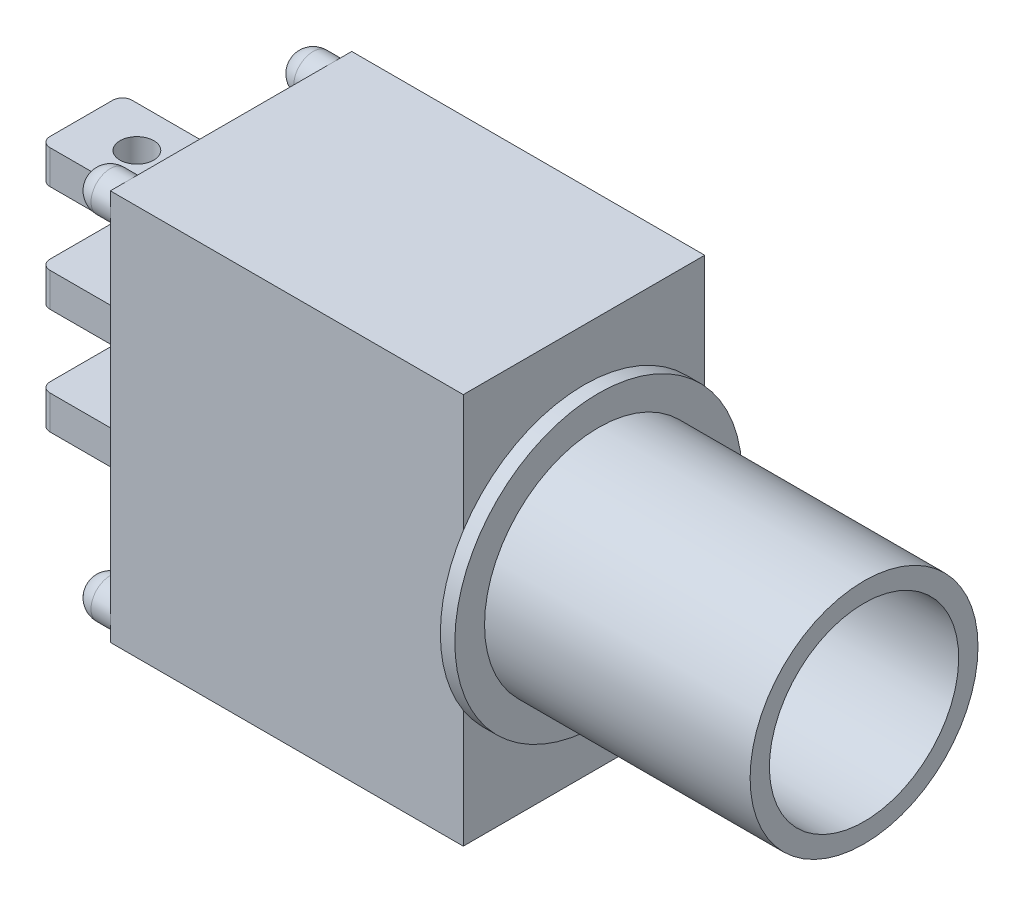
SolidWorks part; units mm, degrees
ref_plane "Front Plane" through (0, 0, 0) normal (0, 0, 1) x (1, 0, 0)
ref_plane "Top Plane" through (0, 0, 0) normal (0, 1, 0) x (1, 0, 0)
ref_plane "Right Plane" through (0, 0, 0) normal (1, 0, 0) x (0, 0, -1)
sketch "Sketch1" plane through (0, 0, 0) normal (0, 0, 1) x (1, 0, 0)
  line L1 (-3.655, 4.05) -> (3.655, 4.05)
  line L2 (-3.655, 4.05) -> (-3.655, -4.05)
  line L3 (-3.655, -4.05) -> (3.655, -4.05)
  line L4 (3.655, 4.05) -> (3.655, -4.05)
  line L5 (-3.655, 4.05) -> (3.655, -4.05) construction
  line L6 (-3.655, -4.05) -> (3.655, 4.05) construction
  point P0 (0, 0)
  dimension "D1" = 7.31
  dimension "D2" = 8.1
extrude "Boss-Extrude1" add sketch "Sketch1" along normal blind 2.5 and the other way blind 2.5
sketch "Sketch2" plane through (-3.655, 0, 0) normal (-1, 0, 0) x (0, 0, 1)
  line L0 (-2.5, 4.05) -> (2.5, 4.05) construction
  line L1 (2.5, 4.05) -> (2.5, -4.05) construction
  line L2 (0, 4.05) -> (0, -4.05) construction
  line L3 (-2.5, -4.05) -> (2.5, -4.05) construction
  line L4 (-2.5, 0) -> (2.5, 0) construction
  line L5 (-2.5, 4.05) -> (-2.5, -4.05) construction
  circle A0 centre (2.1, 3.65) radius 0.4
  circle A1 centre (2.1, -3.65) radius 0.4
  circle A2 centre (-2.1, -3.65) radius 0.4
  circle A3 centre (-2.1, 3.65) radius 0.4
  dimension "D1" = 0.8
extrude "Boss-Extrude2" add sketch "Sketch2" along normal blind 0.8
fillet "Fillet1" radius 0.4 4 edges at (-4.455, -4.05, -2.1) (-4.455, -3.25, 2.1) (-4.455, 3.25, 2.1) (-4.455, 4.05, -2.1)
sketch "Sketch3" plane through (0, 0, 0) normal (0, 1, 0) x (1, 0, 0)
  line L0 (-3.655, 2.1) -> (-3.655, -2.1) construction
  line L1 (-3.655, 1.55) -> (-4.455, 1.55)
  line L2 (-3.655, 1.55) -> (-3.655, -1.55)
  line L3 (-3.655, -1.55) -> (-4.455, -1.55)
  line L4 (-6.755, 0.85) -> (-4.455, 1.55) construction
  line L5 (-3.655, 1.55) -> (-3.655, -0.0473) construction
  line L6 (-3.655, -1.55) -> (-3.655, -0.0473) construction
  line L7 (-4.455, 1.55) -> (-4.455, 0.85)
  line L8 (-4.455, 0.85) -> (-6.755, 0.85)
  line L10 (-4.455, -0.85) -> (-6.755, -0.85)
  line L11 (-6.755, 0.85) -> (-6.755, -0.85)
  line L12 (-6.755, -0.85) -> (-4.455, -1.55) construction
  line L13 (-4.455, -0.85) -> (-4.455, -1.55)
  circle A0 centre (-5.605, 0) radius 0.35
  point P0 (-3.655, 0)
  dimension "D5" = 0.7
  dimension "D1" = 3.1
  dimension "D2" = 0.8
  dimension "D3" = 1.7
  dimension "D4" = 2.3
extrude "Boss-Extrude3" add sketch "Sketch3" along normal blind 0.35 and the other way blind 0.35
pattern_linear "LPattern1" count 2 spacing 2.2 along (0, -1, 0) of "Boss-Extrude3"
pattern_linear "LPattern2" count 2 spacing 2.2 along (0, 1, 0) of "Boss-Extrude3"
fillet "Fillet2" radius 0.2 18 edges at (-4.455, -2.2, -1.55) (-4.455, -2.2, -0.85) (-6.755, -2.2, -0.85) (-6.755, -2.2, 0.85) (-4.455, -2.2, 0.85) (-4.455, -2.2, 1.55) (-4.455, 0, 1.55) (-4.455, 0, 0.85) (-6.755, 0, 0.85) (-6.755, 0, -0.85) (-4.455, 0, -0.85) (-4.455, 0, -1.55) (-4.455, 2.2, 1.55) (-4.455, 2.2, 0.85) (-4.455, 2.2, -1.55) (-4.455, 2.2, -0.85) (-6.755, 2.2, 0.85) (-6.755, 2.2, -0.85)
sketch "Sketch4" plane through (3.655, 0, 0) normal (1, 0, 0) x (0, 0, -1)
  circle A0 centre (0, 0) radius 2.975
  dimension "D1" = 5.95
extrude "Boss-Extrude4" add sketch "Sketch4" along normal blind 0.3
sketch "Sketch5" plane through (3.955, 0, 0) normal (1, 0, 0) x (0, 0, -1)
  circle A0 centre (0, 0) radius 2.36
  dimension "D1" = 4.72
extrude "Boss-Extrude5" add sketch "Sketch5" along normal blind 5.5
shell "Shell1" thickness 0.4 removed face at (9.455, 2.36, 0)
